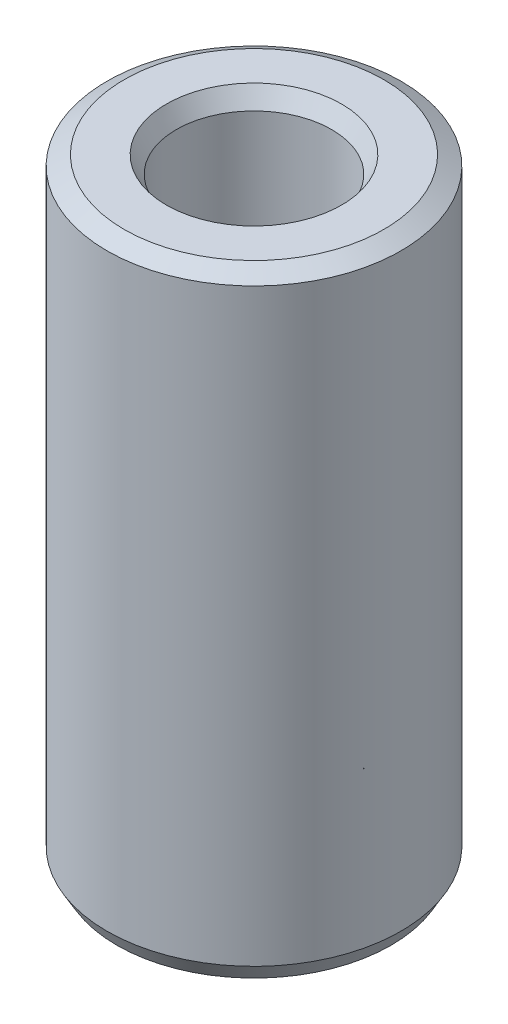
SolidWorks part; units mm, degrees
ref_plane "Front Plane" through (0, 0, 0) normal (0, 0, 1) x (1, 0, 0)
ref_plane "Top Plane" through (0, 0, 0) normal (0, 1, 0) x (1, 0, 0)
ref_plane "Right Plane" through (0, 0, 0) normal (1, 0, 0) x (0, 0, -1)
sketch "Sketch1" plane through (0, 0, 0) normal (0, 1, 0) x (1, 0, 0)
  circle A0 centre (0, 0) radius 27.5
  dimension "SLEEVE_OD" = 55
extrude "Boss-Extrude1" add sketch "Sketch1" along normal blind 115.3091
sketch "Sketch2" plane through (0, 0, 0) normal (0, 1, 0) x (1, 0, 0)
  circle A0 centre (0, 0) radius 14.5363
  dimension "BORE_D" = 29.0727
extrude "Cut-Extrude1" cut sketch "Sketch2" along normal through all
chamfer "Chamfer1" distance 1.854 angle 60 4 edges at (0, 115.3091, 14.5363) (0, 0, 14.5363) (0, 0, 27.5) (0, 115.3091, 27.5) first distance on face at (0, 115.3091, 14.5363) first distance on face at (0, 0, 14.5363) first distance on face at (0, 115.3091, 27.5)
